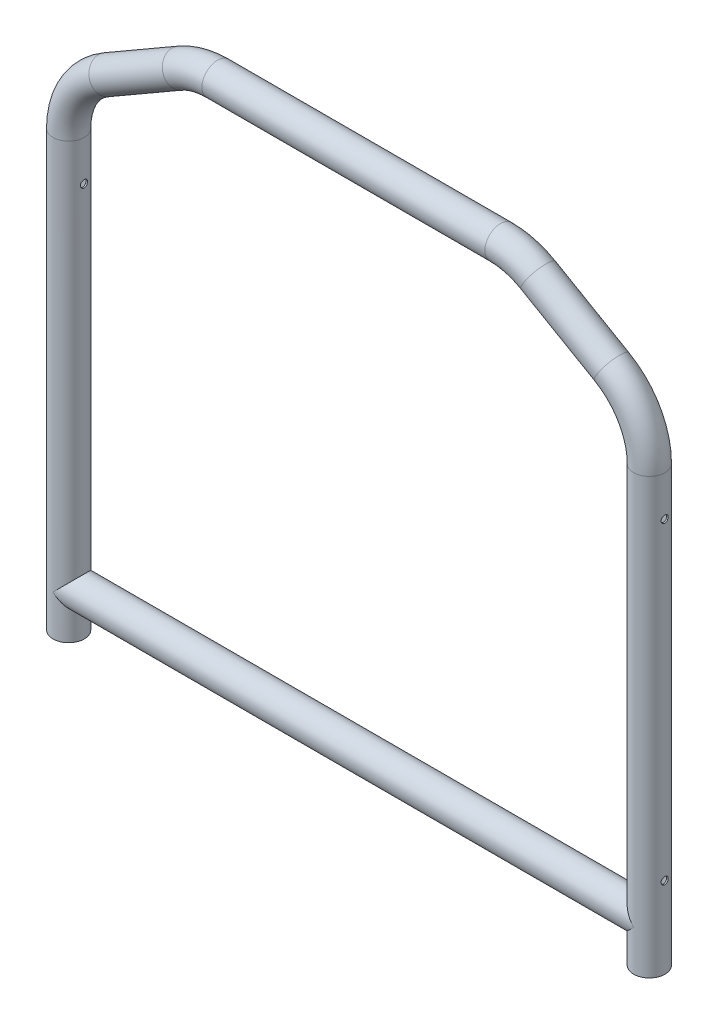
SolidWorks part; units mm, degrees
ref_plane "Front Plane" through (0, 0, 0) normal (0, 0, 1) x (1, 0, 0)
ref_plane "Top Plane" through (0, 0, 0) normal (0, 1, 0) x (1, 0, 0)
ref_plane "Right Plane" through (0, 0, 0) normal (1, 0, 0) x (0, 0, -1)
sketch "Sketch1" plane through (0, 0, 0) normal (0, 0, 1) x (1, 0, 0)
  line L0 (-99.3894, 0) -> (99.3894, 0)
  line L1 (125.8894, -7.1007) -> (177.5, -36.898)
  line L2 (204, -82.7974) -> (204, -388)
  line L3 (0, 0) -> (0, -391.4251) construction
  line L4 (-204, -82.7974) -> (-204, -388)
  line L5 (-125.8894, -7.1007) -> (-177.5, -36.898)
  arc A0 (204, -82.7974) -> (177.5, -36.898) centre (151, -82.7974) ccw
  arc A1 (125.8894, -7.1007) -> (99.3894, 0) centre (99.3894, -53) ccw
  arc A2 (-125.8894, -7.1007) -> (-99.3894, 0) centre (-99.3894, -53) cw
  arc A3 (-204, -82.7974) -> (-177.5, -36.898) centre (-151, -82.7974) cw
  dimension "D2" = 53
  dimension "D1" = 388
  dimension "D3" = 150
  dimension "D4" = 204
ref_plane "Plane1" through (204, -388, 0) normal (0, -1, 0) x (-1, 0, 0)
sketch "Sketch2" plane through (204, -388, 0) normal (0, -1, 0) x (-1, 0, 0)
  line L0 (0, 0) -> (26.5, 0) construction
  circle A0 centre (0, 0) radius 11
  circle A1 centre (0, 0) radius 10
  dimension "D1" = 1
sweep "Sweep1" add profiles "Sketch2" path "Sketch1"
sketch "Sketch3" plane through (0, 0, 0) normal (1, 0, 0) x (0, 0, -1)
  circle A0 centre (0, -359.3992) radius 11
  circle A1 centre (0, -359.3992) radius 10
  dimension "D1" = 1
extrude "Boss-Extrude1" add sketch "Sketch3" along normal up to surface and the other way up to surface up to face at (215, -388, 0) other way up to face at (-215, -82.7974, 0)
sketch "Sketch4" plane through (0, -388, 0) normal (0, -1, 0) x (1, 0, 0)
  line L0 (-204, 0) -> (-214, 0) construction
  circle A0 centre (-204, 0) radius 10 construction
ref_plane "Plane2" through (-204, -388, 0) normal (-1, 0, 0) x (0, 0, 1)
sketch "Sketch5" plane through (-204, -388, 0) normal (-1, 0, 0) x (0, 0, 1)
  circle A0 centre (0, 57) radius 2.5
  circle A1 centre (0, 388) radius 11 construction
  dimension "D1" = 331
extrude "Cut-Extrude1" cut sketch "Sketch5" along normal blind 200
sketch "Sketch6" plane through (-204, -388, 0) normal (-1, 0, 0) x (0, 0, 1)
  circle A0 centre (0, 277) radius 2.5
  circle A1 centre (0, 388) radius 11 construction
  dimension "D1" = 111
extrude "Cut-Extrude2" cut sketch "Sketch6" against normal blind 200 and the other way blind 200
mirror "Mirror1" about plane through (0, 0, 0) normal (1, 0, 0) of "Cut-Extrude2", "Cut-Extrude1"
